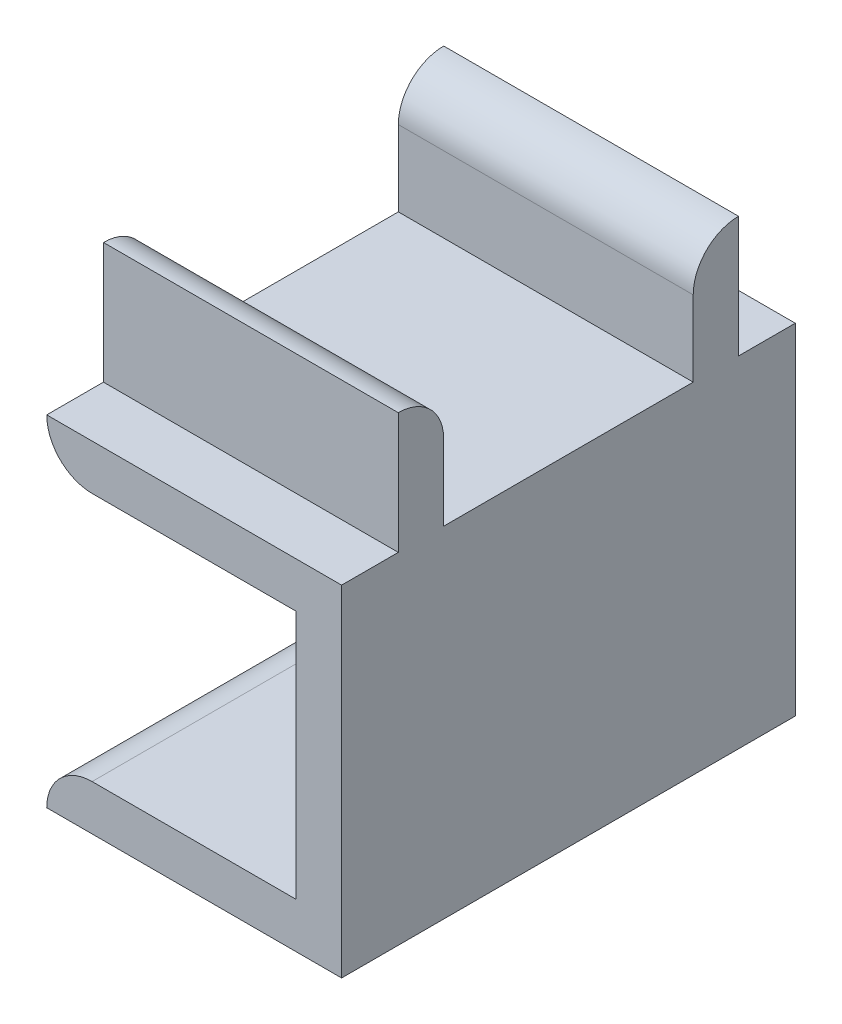
SolidWorks part; units mm, degrees
ref_plane "Front Plane" through (0, 0, 0) normal (0, 0, 1) x (1, 0, 0)
ref_plane "Top Plane" through (0, 0, 0) normal (0, 1, 0) x (1, 0, 0)
ref_plane "Right Plane" through (0, 0, 0) normal (1, 0, 0) x (0, 0, -1)
sketch "Sketch1" plane through (0, 0, 0) normal (0, 0, 1) x (1, 0, 0)
  line L0 (0, 0) -> (0, 22.5)
  line L1 (0, 22.5) -> (-19.5, 22.5)
  line L2 (-19.5, 22.5) -> (-19.5, 19.5)
  line L3 (-19.5, 19.5) -> (-3, 19.5)
  line L4 (-3, 19.5) -> (-3, 3)
  line L5 (-3, 3) -> (-19.5, 3)
  line L6 (-19.5, 3) -> (-19.5, 0)
  line L7 (-19.5, 0) -> (0, 0)
  dimension "D1" = 16.5
  dimension "D2" = 16.5
  dimension "D3" = 16.5
  dimension "D4" = 3
  dimension "D5" = 3
  dimension "D6" = 3
extrude "Boss-Extrude1" add sketch "Sketch1" along normal blind 30
sketch "Sketch2" plane through (0, 22.5, 0) normal (0, 1, 0) x (1, 0, 0)
  line L0 (0, -15) -> (-19.5, -15) construction
  line L1 (0, -30) -> (0, 0) construction
  line L2 (-19.5, -30) -> (-19.5, 0) construction
  line L3 (-19.5, -15) -> (0, -15) construction
  line L5 (0, -3.75) -> (-19.5, -3.75)
  line L6 (0, -3.75) -> (0, -6.75)
  line L7 (0, -6.75) -> (-19.5, -6.75)
  line L8 (-19.5, -3.75) -> (-19.5, -6.75)
  line L9 (0, -23.25) -> (-19.5, -23.25)
  line L10 (0, -23.25) -> (0, -26.25)
  line L11 (0, -26.25) -> (-19.5, -26.25)
  line L12 (-19.5, -23.25) -> (-19.5, -26.25)
  dimension "D1" = 8.25
  dimension "D2" = 8.25
  dimension "D3" = 3
  dimension "D4" = 3
extrude "Boss-Extrude2" add sketch "Sketch2" along normal blind 8
fillet "Fillet1" radius 3 1 edges at (-9.75, 30.5, 6.75)
fillet "Fillet2" radius 3 1 edges at (-9.75, 30.5, 23.25)
fillet "Fillet3" radius 3 1 edges at (-19.5, 19.5, 15)
fillet "Fillet4" radius 3 1 edges at (-19.5, 3, 15)
